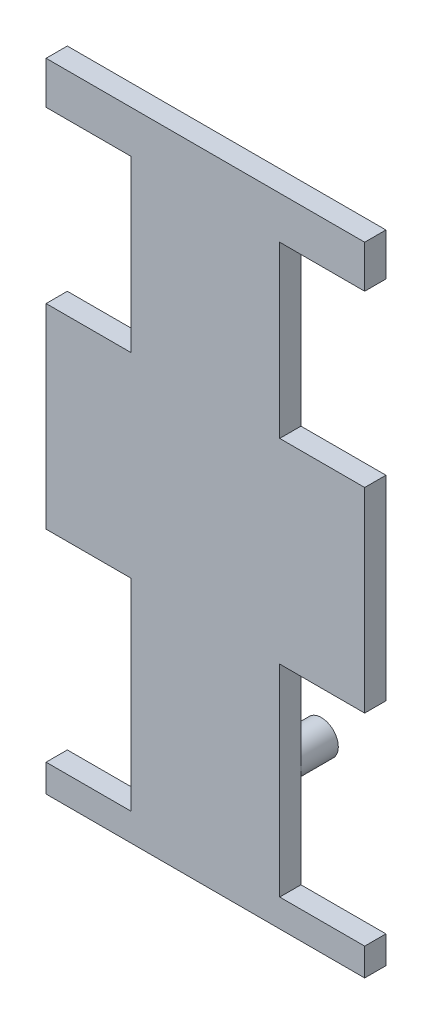
SolidWorks part; units mm, degrees
ref_plane "Front Plane" through (0, 0, 0) normal (0, 0, 1) x (1, 0, 0)
ref_plane "Top Plane" through (0, 0, 0) normal (0, 1, 0) x (1, 0, 0)
ref_plane "Right Plane" through (0, 0, 0) normal (1, 0, 0) x (0, 0, -1)
sketch "Sketch2" plane through (0, 0, 0) normal (0, 0, 1) x (1, 0, 0)
  line L0 (-180, 280) -> (-180, 200) construction
  line L1 (0, 0) -> (-150, 0)
  line L2 (0, 0) -> (0, 20)
  line L3 (0, 300) -> (-150, 300)
  line L4 (-150, 0) -> (-150, 20)
  line L5 (-180, 100) -> (-180, 20) construction
  line L6 (30, 280) -> (30, 200) construction
  line L7 (30, 100) -> (30, 20) construction
  line L8 (-180, 280) -> (-150, 280) construction
  line L9 (-180, 200) -> (-150, 200) construction
  line L10 (30, 280) -> (0, 280) construction
  line L11 (30, 200) -> (0, 200) construction
  line L12 (-180, 100) -> (-150, 100) construction
  line L13 (-180, 20) -> (-150, 20) construction
  line L14 (30, 100) -> (0, 100) construction
  line L15 (30, 20) -> (0, 20) construction
  line L16 (0, 280) -> (0, 300)
  line L17 (-150, 280) -> (-110, 280)
  line L19 (-150, 200) -> (-110, 200)
  line L20 (-110, 280) -> (-110, 200)
  line L21 (0, 280) -> (-40, 280)
  line L23 (0, 200) -> (-40, 200)
  line L24 (-40, 280) -> (-40, 200)
  line L25 (-150, 100) -> (-110, 100)
  line L27 (-150, 20) -> (-110, 20)
  line L28 (-110, 100) -> (-110, 20)
  line L29 (0, 100) -> (-40, 100)
  line L31 (0, 20) -> (-40, 20)
  line L32 (-40, 100) -> (-40, 20)
  line L33 (-150, 280) -> (-150, 300)
  line L34 (-150, 100) -> (-150, 200)
  line L35 (0, 100) -> (0, 200)
  dimension "D1" = 300
  dimension "D2" = 80
  dimension "D3" = 150
  dimension "D4" = 20
  dimension "D5" = 20
  dimension "D6" = 30
  dimension "D7" = 30
  dimension "D8" = 40
extrude "Boss-Extrude1" add sketch "Sketch2" along normal blind 10
sketch "Sketch5" plane through (0, 0, 0) normal (0, 0, -1) x (-1, 0, 0)
  line L0 (48.4216, 60) -> (40, 60) construction
  line L1 (40, 20) -> (40, 100) construction
  line L2 (101.5784, 60) -> (110, 60) construction
  line L3 (110, 100) -> (110, 20) construction
  line L4 (48.4216, 60) -> (40, 20) construction
  line L5 (48.4216, 60) -> (40, 100) construction
  circle A0 centre (48.4216, 60) radius 8
  circle A1 centre (101.5784, 60) radius 8
  dimension "D1" = 16
extrude "Boss-Extrude3" add sketch "Sketch5" along normal blind 18
sketch "Sketch6" plane through (0, 0, 0) normal (0, 0, -1) x (-1, 0, 0)
  line L0 (0, 0) -> (0, 20) construction
  line L1 (0, 100) -> (40, 100)
  line L2 (0, 100) -> (0, 108)
  line L3 (0, 108) -> (40, 108)
  line L4 (40, 100) -> (40, 108)
  line L5 (150, 100) -> (110, 100)
  line L6 (150, 100) -> (150, 108)
  line L7 (150, 108) -> (110, 108)
  line L8 (110, 100) -> (110, 108)
  line L9 (40, 20) -> (0, 20)
  line L10 (40, 20) -> (40, 13)
  line L11 (40, 13) -> (0, 13)
  line L12 (0, 20) -> (0, 13)
  line L14 (150, 20) -> (110, 20)
  line L15 (150, 20) -> (150, 13)
  line L16 (150, 13) -> (110, 13)
  line L17 (110, 20) -> (110, 13)
  dimension "D1" = 8
  dimension "D2" = 7
extrude "Cut-Extrude1" cut sketch "Sketch6" against normal through all
